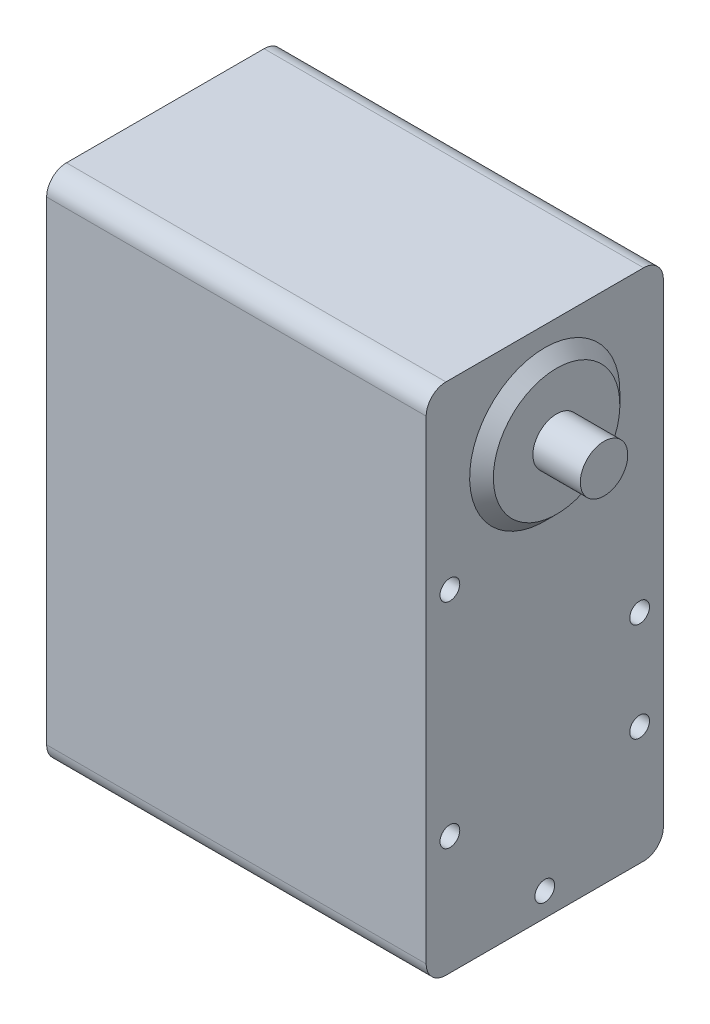
SolidWorks part; units mm, degrees
ref_plane "Front Plane" through (0, 0, 0) normal (0, 0, 1) x (1, 0, 0)
ref_plane "Top Plane" through (0, 0, 0) normal (0, 1, 0) x (1, 0, 0)
ref_plane "Right Plane" through (0, 0, 0) normal (1, 0, 0) x (0, 0, -1)
sketch "Sketch1" plane through (0, 0, 0) normal (0, 0, 1) x (1, 0, 0)
  line L0 (-113.25, 0) -> (116.4643, 0) construction
  line L2 (-24, -32.5) -> (24, -32.5)
  line L3 (-24, -32.5) -> (-24, 32.5)
  line L4 (-24, 32.5) -> (24, 32.5)
  line L5 (24, -32.5) -> (24, 32.5)
  point P7 (0, 32.5)
  point P8 (24, 0)
  dimension "D1" = 48
  dimension "D2" = 65
extrude "Boss-Extrude1" add sketch "Sketch1" along normal blind 15 and the other way blind 15
sketch "Sketch2" plane through (-24, 0, 0) normal (-1, 0, 0) x (0, 0, 1)
  line L0 (12, 29.5) -> (-12, 29.5) construction
  line L1 (-12, 29.5) -> (-12, 5.5) construction
  line L2 (-12, 5.5) -> (-12, -29.5) construction
  line L3 (-12, -29.5) -> (12, -29.5) construction
  line L4 (12, -29.5) -> (12, 5.5) construction
  line L5 (12, 5.5) -> (12, 29.5) construction
  line L6 (0, 29.5) -> (0, 32.5) construction
  line L7 (0, 32.5) -> (16.6874, 32.5) construction
  line L8 (-15, 32.5) -> (15, 32.5) construction
  circle A0 centre (-12, 29.5) radius 1.25
  circle A1 centre (12, 29.5) radius 1.25
  circle A2 centre (12, 5.5) radius 1.25
  circle A3 centre (-12, 5.5) radius 1.25
  circle A4 centre (-12, -29.5) radius 1.25
  circle A5 centre (12, -29.5) radius 1.25
  dimension "D1" = 2.5
  dimension "D2" = 2.5
  dimension "D3" = 2.5
  dimension "D4" = 2.5
  dimension "D5" = 2.5
  dimension "D6" = 2.5
extrude "Cut-Extrude1" cut sketch "Sketch2" against normal blind 10
sketch "Sketch4" plane through (-24, 0, 0) normal (-1, 0, 0) x (0, 0, 1)
  line L0 (0, 20.5) -> (0, 32.5) construction
  line L1 (-15, 32.5) -> (15, 32.5) construction
  circle A0 centre (0, 20.5) radius 9.5
  circle A1 centre (0, 20.5) radius 8
  circle A2 centre (0, 20.5) radius 3
  point P7 (0, 32.5)
extrude "Boss-Extrude3" add sketch "Sketch4" along normal blind 1.5 contours A0 A1 | A1 A2 | A2 region at (-24, 20.5, -9.2313) region at (-24, 20.5, -7.7737) region at (-24, 20.5, 0)
chamfer "Chamfer2" distance 1.5 angle 45 1 edges at (-25.5, 11, 0)
sketch "Sketch5" plane through (-25.5, 0, 0) normal (-1, 0, 0) x (0, 0, 1)
  circle A0 centre (0, 20.5) radius 3
extrude "Boss-Extrude4" add sketch "Sketch5" along normal blind 6
mirror "Mirror1" about plane through (0, 0, 0) normal (1, 0, 0) of "Boss-Extrude4", "Chamfer2", "Boss-Extrude3"
sketch "Sketch6" plane through (24, 0, 0) normal (1, 0, 0) x (0, 0, -1)
  line L0 (-12, 9.5) -> (12, 9.5)
  line L1 (12, 9.5) -> (12, -22.7311)
  line L2 (12, -22.7311) -> (5.2311, -29.5)
  line L3 (5.2311, -29.5) -> (-7.9002, -29.5)
  line L4 (-7.9002, -29.5) -> (-12, -20.4737)
  line L5 (-12, -20.4737) -> (-12, 9.5)
  line L6 (0, 9.5) -> (0, 32.5)
  line L7 (-15, 32.5) -> (0, 32.5) construction
  line L8 (15, 32.5) -> (-15, 32.5) construction
  circle A0 centre (12, -5) radius 1.25
  circle A1 centre (12, -17.5) radius 1.25
  circle A2 centre (0, -29.5) radius 1.25
  circle A3 centre (-12, -17.5) radius 1.25
  circle A4 centre (-12, 9.5) radius 1.25
  point P17 (0, 0)
  point P18 (0, 0)
  point P19 (0, 0)
  point P21 (0, 0)
  point P25 (0, 0)
  dimension "D1" = 14.5
  dimension "D2" = 27
  dimension "D3" = 5.2311
  dimension "D4" = 5.2311
extrude "Cut-Extrude2" cut sketch "Sketch6" against normal blind 10 contours A4 | A3 | A2 | A1 | A0
fillet "Fillet1" radius 2.5 4 edges at (0, 32.5, -15) (0, 32.5, 15) (0, -32.5, -15) (0, -32.5, 15)
